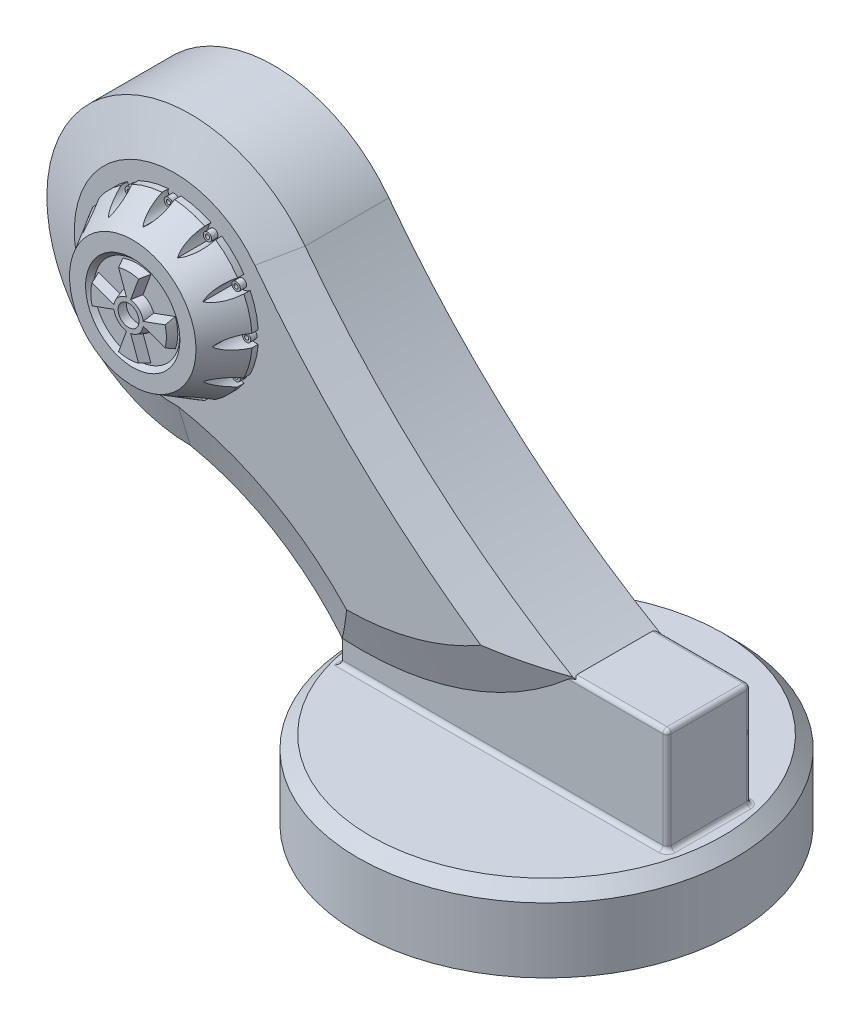
SolidWorks part; units mm, degrees
material "6061-T6 (SS)"
ref_plane "Front Plane" through (0, 0, 0) normal (0, 0, 1) x (1, 0, 0)
ref_plane "Top Plane" through (0, 0, 0) normal (0, 1, 0) x (1, 0, 0)
ref_plane "Right Plane" through (0, 0, 0) normal (1, 0, 0) x (0, 0, -1)
sketch "Sketch1" plane through (0, 0, 0) normal (0, 1, 0) x (1, 0, 0)
  circle A0 centre (0, 0) radius 90
  dimension "D1" = 180
extrude "Boss-Extrude1" add sketch "Sketch1" along normal blind 37
chamfer "Chamfer1" distance 6 angle 45 1 edges at (0, 37, 90)
sketch "Sketch2" plane through (0, 37, 0) normal (0, 1, 0) x (1, 0, 0)
  line L1 (77.5, 20) -> (-77.5, 20)
  line L2 (77.5, 20) -> (77.5, -20)
  line L3 (77.5, -20) -> (-77.5, -20)
  line L4 (-77.5, 20) -> (-77.5, -20)
  line L5 (77.5, 20) -> (-77.5, -20) construction
  line L6 (77.5, -20) -> (-77.5, 20) construction
  point P0 (0, 0)
  dimension "D1" = 155
  dimension "D2" = 40
extrude "Boss-Extrude2" add sketch "Sketch2" along normal blind 50
sketch "Sketch3" plane through (0, 0, 20) normal (0, 0, 1) x (1, 0, 0)
  line L0 (-77.5, 87) -> (32.5, 87)
  line L1 (-77.5, 87) -> (77.5, 87) construction
  line L2 (-77.5, 87) -> (-77.5, 48)
  line L3 (-77.5, 87) -> (-77.5, 37) construction
  arc A0 (32.5, 87) -> (-77.5, 48) centre (-68.6761, 197.7402) cw
  dimension "D3" = 150
  dimension "D1" = 39
  dimension "D2" = 110
extrude "Cut-Extrude1" cut sketch "Sketch3" against normal through all
sketch "Sketch4" plane through (0, 0, 0) normal (0, 0, 1) x (1, 0, 0)
  line L0 (0, 0) -> (-150, 0)
  line L1 (-150, 0) -> (-150, 160)
  circle A0 centre (-150, 160) radius 68.5
  arc A1 (-150, 91.5) -> (-77.5, 48) centre (-174.2724, -31.1207) cw
  arc A2 (-95.2795, 201.2057) -> (32.5, 87) centre (256.2101, 465.8849) ccw
  arc A3 (32.5, 87) -> (-77.5, 48) centre (-68.6761, 197.7402) cw
  dimension "D3" = 137
  dimension "D4" = 440
  dimension "D5" = 125
  dimension "D6" = 150
  dimension "D1" = 150
  dimension "D2" = 160
extrude "Boss-Extrude3" add sketch "Sketch4" along normal mid plane 40 contours A3 A2 A0 A1 | A0 region at (-102.9332, 112.9332, 0) region at (-53.6276, 98.2483, 0)
sketch "Sketch5" plane through (0, 0, 20) normal (0, 0, 1) x (1, 0, 0)
  circle A0 centre (-150, 160) radius 68.5 construction
  circle A1 centre (-150, 160) radius 68.5
  arc A2 (-77.5, 48) -> (-150, 91.5) centre (-174.2724, -31.1207) ccw construction
  arc A3 (-77.5, 48) -> (-150, 91.5) centre (-174.2724, -31.1207) ccw
  arc A4 (-95.2795, 201.2057) -> (32.5, 87) centre (256.2101, 465.8849) ccw construction
  arc A5 (-95.2795, 201.2057) -> (32.5, 87) centre (256.2101, 465.8849) ccw
  arc A6 (-77.5, 48) -> (32.5, 87) centre (-68.6761, 197.7402) ccw construction
  arc A7 (-77.5, 48) -> (32.5, 87) centre (-68.6761, 197.7402) ccw
  arc M2 (32.5, 87) -> (-95.2795, 201.2057) centre (256.2101, 465.8849) cw
  arc M3 (-95.2795, 201.2057) -> (-150, 91.5) centre (-150, 160) ccw
  arc M4 (-150, 91.5) -> (-77.5, 48) centre (-174.2724, -31.1207) cw
extrude "Boss-Extrude4" add sketch "Sketch5" along normal blind 7.5 draft 70 contours A7 A1 M4 M2 | A1 M3 region at (-150, 160, 20) region at (-53.6276, 98.2483, 20)
sketch "Sketch6" plane through (0, 0, 27.5) normal (0, 0, 1) x (1, 0, 0)
  circle A0 centre (-150, 160) radius 40
  dimension "D1" = 80
extrude "Boss-Extrude5" add sketch "Sketch6" along normal blind 3
sketch "Sketch7" plane through (0, 0, 30.5) normal (0, 0, 1) x (1, 0, 0)
  circle A1 centre (-150, 160) radius 40
  circle A2 centre (-150, 160) radius 40
  dimension "D1" = 0
extrude "Boss-Extrude6" add sketch "Sketch7" along normal blind 17 draft 30
sketch "Sketch8" plane through (0, 0, 47.5) normal (0, 0, 1) x (1, 0, 0)
  line L0 (-150, 160) -> (-150, 222.6115) construction
  circle A0 centre (-150, 160) radius 40 construction
  arc A1 (-147, 199.8873) -> (-153, 199.8873) centre (-150, 160) ccw
  arc A2 (-150, 193) -> (-153, 199.8873) centre (-146.0846, 198.8025) cw
  circle A3 centre (-150, 160) radius 40 construction
  arc A4 (-150, 193) -> (-147, 199.8873) centre (-153.9154, 198.8025) ccw
  point P7 (-150, 200)
  dimension "D2" = 7
  dimension "D1" = 7
  dimension "D3" = 3
extrude "Cut-Extrude2" cut sketch "Sketch8" against normal up to surface (20 mm away) up to face at (-110, 160, 27.5)
sketch "Sketch9" plane through (0, 0, 27.5) normal (0, 0, 1) x (1, 0, 0)
  line L0 (-150, 193) -> (-150, 207.8939) construction
  arc A0 (-153, 199.8873) -> (-150, 193) centre (-146.0846, 198.8025) ccw construction
  arc A1 (-150, 193) -> (-147, 199.8873) centre (-153.9154, 198.8025) ccw construction
  arc A2 (-153, 199.8873) -> (-150, 193) centre (-146.0846, 198.8025) ccw
  arc A3 (-150, 193) -> (-147, 199.8873) centre (-153.9154, 198.8025) ccw
  arc A4 (-111.7404, 188.8103) -> (-148.236, 112.1386) centre (-150, 160) ccw construction
  circle A5 centre (-150, 197.3217) radius 2
  circle A6 centre (-150, 197.3217) radius 1
  dimension "D1" = 4
  dimension "D2" = 2
extrude "Boss-Extrude7" add sketch "Sketch9" along normal blind 3 contours L0 A5 A6 | A5 L0 A6 region at (-151.9553, 197.3217, 27.5) region at (-149.9553, 195.8217, 27.5)
pattern_circular "CirPattern1" count 12 over 360 about axis through (-150, 160, 47.5) along (0, 0, 1) of "Boss-Extrude7", "Cut-Extrude2"
sketch "Sketch10" plane through (0, 0, 47.5) normal (0, 0, 1) x (1, 0, 0)
  circle A0 centre (-150, 160) radius 22.5
  dimension "D1" = 45
extrude "Cut-Extrude3" cut sketch "Sketch10" against normal blind 2 draft 45
sketch "Sketch11" plane through (0, 0, 45.5) normal (0, 0, 1) x (1, 0, 0)
  line L0 (-150, 160) -> (-150, 179.5) construction
  line L1 (-152.9072, 167.9874) -> (-156.6694, 178.324)
  line L2 (-147.0928, 167.9874) -> (-143.3306, 178.324)
  line L3 (-142.0126, 162.9072) -> (-131.676, 166.6694)
  line L4 (-142.0126, 157.0928) -> (-131.676, 153.3306)
  line L5 (-147.0928, 152.0126) -> (-143.3306, 141.676)
  line L6 (-152.9072, 152.0126) -> (-156.6694, 141.676)
  line L7 (-157.9874, 157.0928) -> (-168.324, 153.3306)
  line L8 (-157.9874, 162.9072) -> (-168.324, 166.6694)
  circle A0 centre (-150, 160) radius 19.5
  arc A1 (-157.9874, 157.0928) -> (-152.9072, 152.0126) centre (-150, 160) ccw
  arc A2 (-152.9072, 167.9874) -> (-157.9874, 162.9072) centre (-150, 160) ccw
  arc A3 (-142.0126, 162.9072) -> (-147.0928, 167.9874) centre (-150, 160) ccw
  arc A4 (-147.0928, 152.0126) -> (-142.0126, 157.0928) centre (-150, 160) ccw
  point P24 (-150, 160)
  dimension "D1" = 39
  dimension "D2" = 17
  dimension "D3" = 20
  dimension "D4" = 4
extrude "Boss-Extrude8" add sketch "Sketch11" along normal blind 4 draft 20 contours L5 A4 L4 A0 L3 A3 L2 L1 A2 L8 L7 A1 L6 region at (-150, 160, 45.5)
sketch "Sketch12" plane through (0, 0, 49.5) normal (0, 0, 1) x (1, 0, 0)
  circle A0 centre (-150, 160) radius 5
  dimension "D1" = 10
extrude "Cut-Extrude4" cut sketch "Sketch12" against normal up to surface (4 mm away) up to face at (-129.5, 160, 45.5)
fillet "Fillet1" radius 2 10 edges at (0, 37, -20) (77.5, 37, 0) (-77.5, 48, 0) (-77.5, 37, 0) (55, 87, 20) (55, 87, -20) (77.5, 62, -20) (77.5, 87, 0) (0, 37, 20) (77.5, 62, 20)
sketch "Sketch13" plane through (0, 0, -20) normal (0, 0, -1) x (-1, 0, 0)
  circle A0 centre (150, 160) radius 15
  dimension "D1" = 30
extrude "Cut-Extrude5" cut sketch "Sketch13" against normal blind 20
sketch "Sketch14" plane through (0, 0, 0) normal (0, -1, 0) x (1, 0, 0)
  circle A0 centre (0, 0) radius 15
  dimension "D1" = 30
extrude "Cut-Extrude6" cut sketch "Sketch14" against normal blind 20
